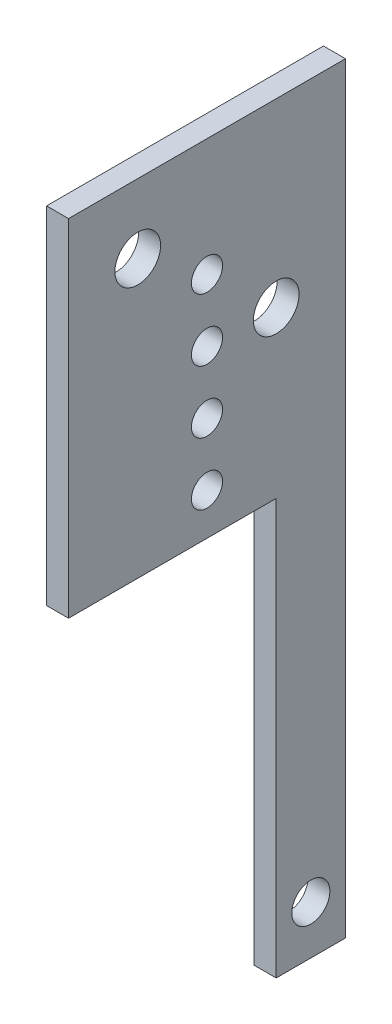
SolidWorks part; units mm, degrees
ref_plane "Front Plane" through (0, 0, 0) normal (0, 0, 1) x (1, 0, 0)
ref_plane "Top Plane" through (0, 0, 0) normal (0, 1, 0) x (1, 0, 0)
ref_plane "Right Plane" through (0, 0, 0) normal (1, 0, 0) x (0, 0, -1)
sketch "Sketch1" plane through (0, 0, 0) normal (1, 0, 0) x (0, 0, -1)
  line L0 (40, 0) -> (0, 0)
  line L2 (0, 0) -> (0, -50)
  line L4 (40, 0) -> (40, -50)
  line L8 (40, -50) -> (40, -110)
  line L9 (40, -110) -> (30, -110)
  line L10 (30, -110) -> (30, -50)
  line L11 (30, -50) -> (0, -50)
  circle A0 centre (30, -26.1084) radius 3.3
  circle A1 centre (10, -10) radius 3.3
  circle A2 centre (20, -16.9748) radius 2.25
  circle A3 centre (20, -25.9748) radius 2.25
  circle A4 centre (20, -34.9748) radius 2.25
  circle A5 centre (20, -43.9748) radius 2.25
  circle A7 centre (35, -103) radius 2.75
  point P17 (0, 0)
  point P26 (35, -110)
  point P27 (0, 0)
  dimension "D3" = 6.6
  dimension "D4" = 6.6
  dimension "D9" = 4.5
  dimension "D10" = 4.5
  dimension "D11" = 4.5
  dimension "D14" = 4.5
  dimension "D7" = 7
  dimension "D17" = 5.5
  dimension "D1" = 50
  dimension "D2" = 40
  dimension "D5" = 10
  dimension "D6" = 60
  dimension "D8" = 10
  dimension "D12" = 9
  dimension "D13" = 9
  dimension "D15" = 9
  dimension "D16" = 20
  dimension "D20" = 10
  dimension "D21" = 50
extrude "Boss-Extrude1" add sketch "Sketch1" along normal blind 3.175
